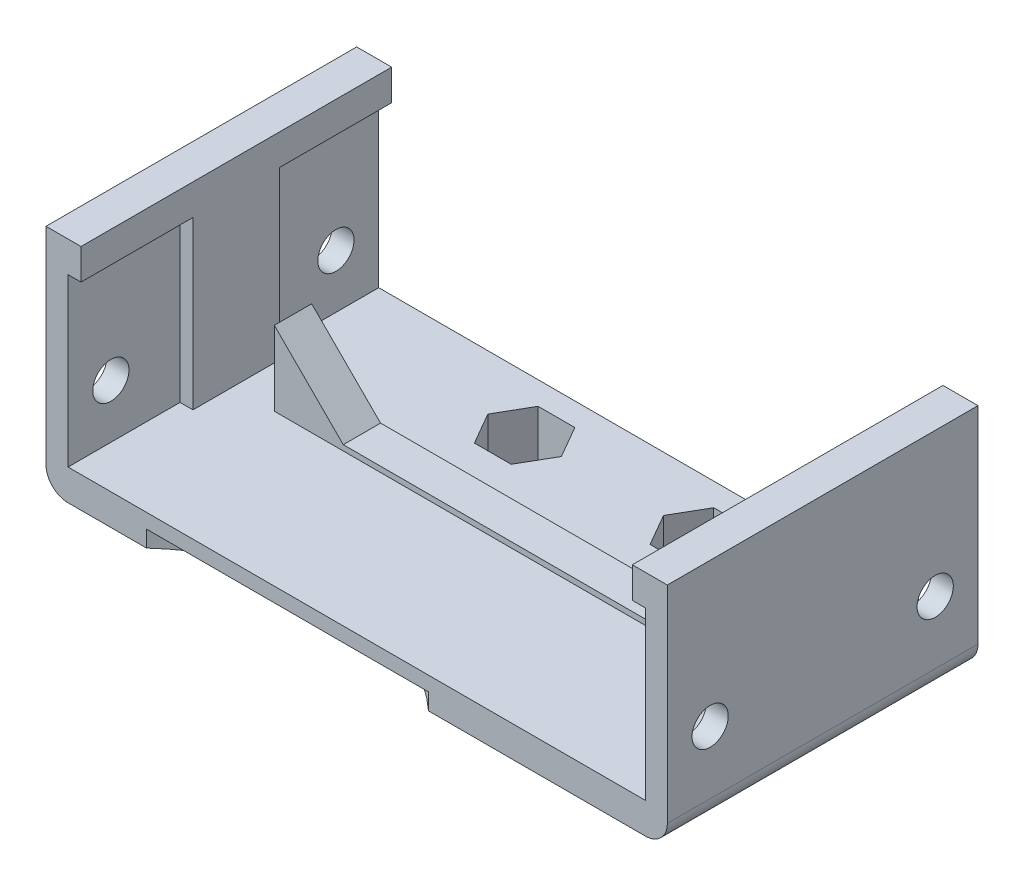
SolidWorks part; units mm, degrees
ref_plane "Front Plane" through (0, 0, 0) normal (0, 0, 1) x (1, 0, 0)
ref_plane "Top Plane" through (0, 0, 0) normal (0, 1, 0) x (1, 0, 0)
ref_plane "Right Plane" through (0, 0, 0) normal (1, 0, 0) x (0, 0, -1)
sketch "Sketch1" plane through (0, 0, 0) normal (0, 0, 1) x (1, 0, 0)
  line L0 (0, 20.81) -> (3.19, 20.81)
  line L1 (0, 20.81) -> (0, 2)
  line L2 (2, 0) -> (54.6, 0)
  line L3 (56.6, 20.81) -> (56.6, 2)
  line L18 (53.41, 20.81) -> (56.6, 20.81)
  line L54 (53.41, 2.82) -> (53.41, 20.81)
  line L55 (3.19, 20.81) -> (3.19, 2.82)
  line L57 (3.19, 2.82) -> (53.41, 2.82)
  arc A0 (54.6, 0) -> (56.6, 2) centre (54.6, 2) ccw
  arc A1 (0, 2) -> (2, 0) centre (2, 2) ccw
extrude "Boss-Extrude1" add sketch "Sketch1" along normal blind 28.3
sketch "Sketch2" plane through (0, 0, 0) normal (0, 0, 1) x (1, 0, 0)
  line L0 (2.01, 18) -> (54.59, 18)
  line L1 (2.01, 18) -> (2.01, 2.82)
  line L2 (2.01, 2.82) -> (54.59, 2.82)
  line L3 (54.59, 18) -> (54.59, 2.82)
extrude "Cut-Extrude1" cut sketch "Sketch2" along normal blind 10.2
extrude "Cut-Extrude2" cut sketch "Sketch2<2>" against normal blind 10.2 from surface starting at face at (28.3, 9.2052, 28.3)
sketch "Sketch2<2>" plane through (0, 0, 0) normal (0, 0, 1) x (1, 0, 0) same geometry as "Sketch2"
sketch "Sketch3" plane through (0, 0, 0) normal (-1, 0, 0) x (0, 0, 1)
  circle A0 centre (3.9, 7.71) radius 1.65
  circle A1 centre (24.4, 7.71) radius 1.65
extrude "Cut-Extrude3" cut sketch "Sketch3" against normal up to surface (56.6 mm away) up to face at (56.6, 11.405, 14.15)
sketch "Sketch4" plane through (0, 0, 0) normal (0, 0, 1) x (1, 0, 0)
  line L0 (7, 9.5982) -> (13.2782, 3.32)
  line L3 (7, 2.82) -> (49.6, 2.82)
  line L5 (13.2782, 3.32) -> (43.3218, 3.32)
  line L6 (43.3218, 3.32) -> (49.6, 9.5982)
  line L8 (7, 2.82) -> (7, 9.5982)
  line L10 (49.6, 2.82) -> (49.6, 9.5982)
extrude "Boss-Extrude2" add sketch "Sketch4" along normal blind 3.4 from offset 11.1
sketch "Sketch5" plane through (0, 0, 0) normal (0, -1, 0) x (1, 0, 0)
  line L4 (34.8452, 28.3) -> (9.1548, 28.3)
  arc A0 (9.1548, 28.3) -> (34.8452, 28.3) centre (22, 42.3) ccw
extrude "Cut-Extrude4" cut sketch "Sketch5" against normal blind 1.5
sketch "Sketch6" plane through (0, 0, 0) normal (0, -1, 0) x (1, 0, 0)
  line L4 (26.0735, 5) -> (23.1868, 10)
  line L11 (23.1868, 10) -> (17.4132, 10)
  line L12 (17.4132, 10) -> (14.5265, 5)
  line L13 (14.5265, 5) -> (17.4132, 0)
  line L14 (17.4132, 0) -> (23.1868, 0)
  line L15 (23.1868, 0) -> (26.0735, 5)
  line L16 (42.0735, 5) -> (39.1868, 10)
  line L17 (39.1868, 10) -> (33.4132, 10)
  line L18 (33.4132, 10) -> (30.5265, 5)
  line L19 (30.5265, 5) -> (33.4132, 0)
  line L20 (33.4132, 0) -> (39.1868, 0)
  line L21 (39.1868, 0) -> (42.0735, 5)
  circle A6 centre (20.3, 5) radius 1.65
  circle A7 centre (36.3, 5) radius 1.65
extrude "Boss-Extrude3" add sketch "Sketch6" along normal blind 6
sketch "Sketch8" plane through (0, -6, 0) normal (0, -1, 0) x (1, 0, 0)
  line L9 (23.6486, 5) -> (21.9743, 7.9)
  line L10 (21.9743, 7.9) -> (18.6257, 7.9)
  line L11 (18.6257, 7.9) -> (16.9514, 5)
  line L12 (16.9514, 5) -> (18.6257, 2.1)
  line L13 (18.6257, 2.1) -> (21.9743, 2.1)
  line L14 (21.9743, 2.1) -> (23.6486, 5)
  line L15 (39.6486, 5) -> (37.9743, 7.9)
  line L16 (37.9743, 7.9) -> (34.6257, 7.9)
  line L17 (34.6257, 7.9) -> (32.9514, 5)
  line L18 (32.9514, 5) -> (34.6257, 2.1)
  line L19 (34.6257, 2.1) -> (37.9743, 2.1)
  line L20 (37.9743, 2.1) -> (39.6486, 5)
extrude "Cut-Extrude5" cut sketch "Sketch8" against normal up to surface (8.82 mm away) from offset 3 up to face at (28.3, 2.82, 14.15) offset against normal yes
